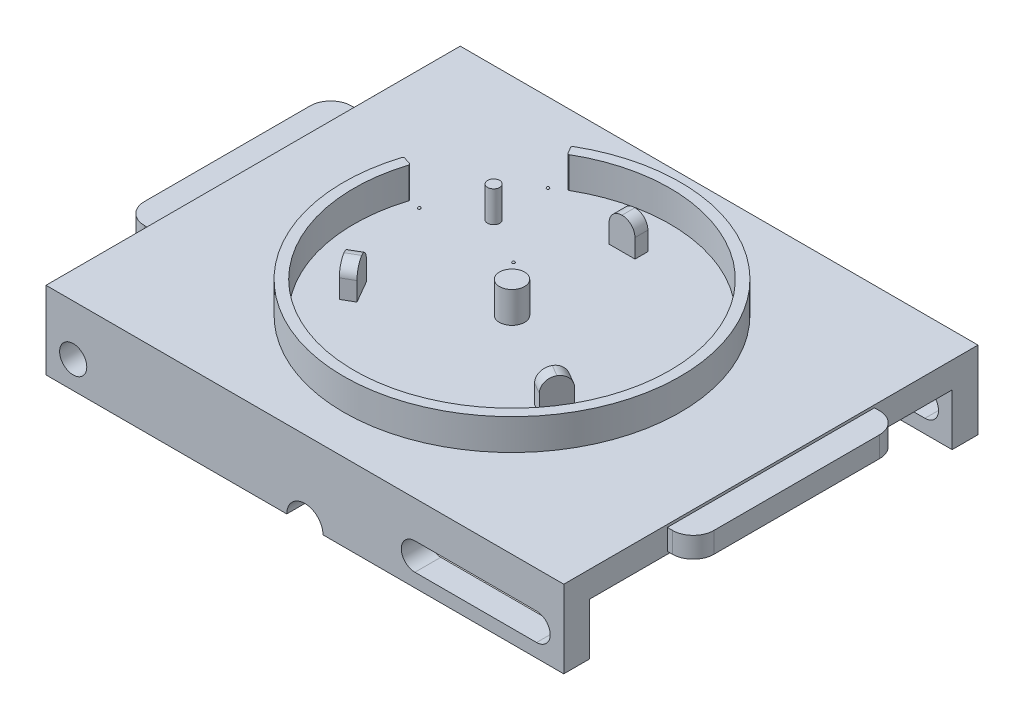
SolidWorks part; units mm, degrees
ref_plane "Vorne" through (0, 0, 0) normal (0, 0, 1) x (1, 0, 0)
ref_plane "Oben" through (0, 0, 0) normal (0, 1, 0) x (1, 0, 0)
ref_plane "Seite" through (0, 0, 0) normal (1, 0, 0) x (0, 0, -1)
sketch "Skizze1" plane through (0, 0, 0) normal (0, 1, 0) x (1, 0, 0)
  line L1 (100, -80) -> (-100, -80)
  line L2 (100, -80) -> (100, 80)
  line L3 (100, 80) -> (-100, 80)
  line L4 (-100, -80) -> (-100, 80)
  line L5 (100, -80) -> (-100, 80) construction
  line L6 (100, 80) -> (-100, -80) construction
  point P0 (0, 0)
  dimension "D1" = 160
  dimension "D2" = 200
extrude "Aufsatz-Linear austragen1" add sketch "Skizze1" along normal mid plane 10
sketch "Skizze2" plane through (0, -5, 0) normal (0, -1, 0) x (-1, 0, 0)
  line L0 (-100, 0) -> (100, 0) construction
  line L5 (100, -75) -> (-100, -75) construction
  line L6 (100, 70) -> (-100, 70)
  line L7 (100, 70) -> (100, 80)
  line L8 (100, 80) -> (-100, 80)
  line L9 (-100, 70) -> (-100, 80)
  line L10 (0, 80) -> (0, 70) construction
  line L15 (-100, -80) -> (-100, 80) construction
  line L16 (100, 80) -> (100, -80) construction
  line L17 (0, -80) -> (0, 80) construction
  line L18 (100, -80) -> (-100, -80) construction
  line L19 (-100, 80) -> (100, 80) construction
  line L20 (100, 75) -> (-100, 75) construction
  line L21 (0, -80) -> (0, -70) construction
  line L22 (-100, -70) -> (-100, -80)
  line L23 (100, -80) -> (-100, -80)
  line L24 (100, -70) -> (100, -80)
  line L25 (100, -70) -> (-100, -70)
  point P28 (0, -75)
  point P672 (0, 75)
  dimension "D1" = 200
  dimension "D2" = 10
  dimension "D3" = 80
extrude "Aufsatz-Linear austragen2" add sketch "Skizze2" along normal blind 20
sketch "Skizze3" plane through (0, 0, 0) normal (0, 0, 1) x (1, 0, 0)
  line L0 (42.5, -9.25) -> (89.5, -9.25)
  line L1 (42.5, -19.75) -> (89.5, -19.75)
  line L2 (100, -25) -> (-100, -25) construction
  line L3 (100, -25) -> (100, 5) construction
  line L4 (-100, -25) -> (-100, 5) construction
  line L5 (-7, -25) -> (7, -25)
  circle A0 centre (-89.5, -14.5) radius 5.25
  arc A1 (89.5, -19.75) -> (89.5, -9.25) centre (89.5, -14.5) ccw
  arc A2 (42.5, -9.25) -> (42.5, -19.75) centre (42.5, -14.5) ccw
  arc A3 (7, -25) -> (-7, -25) centre (0, -25) ccw
  dimension "D2" = 10.5
  dimension "D6" = 7
  dimension "D1" = 10.5
  dimension "D3" = 47
  dimension "D4" = 10.5
  dimension "D5" = 10.5
extrude "Schnitt-Linear austragen1" cut sketch "Skizze3" against normal through all both and the other way through all
sketch "Skizze4" plane through (0, 5, 0) normal (0, 1, 0) x (1, 0, 0)
  line L0 (-58.0351, 18.7863) -> (-61.8407, 20.0182)
  line L1 (-100, 80) -> (-100, -80) construction
  line L2 (-31.0675, 52.4958) -> (-33.1047, 55.9382)
  line L5 (0, 0) -> (-35.4514, 28.3612) construction
  line L6 (-35.4514, 28.3612) -> (-100, 80) construction
  circle A0 centre (0, 0) radius 4.85
  circle A3 centre (-35.4514, 28.3612) radius 2.35
  arc A4 (-61.8407, 20.0182) -> (-33.1047, 55.9382) centre (0, 0) ccw
  arc A5 (-58.0351, 18.7863) -> (-31.0675, 52.4958) centre (0, 0) ccw
  dimension "D1" = 9.7
  dimension "D4" = 4.7
  dimension "D7" = 4
  dimension "D3" = 46
  dimension "D5" = 61
  dimension "D2" = 45.4
extrude "Aufsatz-Linear austragen3" add sketch "Skizze4" along normal blind 12
chamfer "Fase1" distance 0.4 angle 45 4 edges at (-58.0351, 11, -18.7863) (-61.8407, 11, -20.0182) (-33.1047, 11, -55.9382) (-31.0675, 11, -52.4958)
sketch "Skizze6" plane through (0, 5, 0) normal (0, 1, 0) x (1, 0, 0)
  line L0 (0, 45) -> (-38.9711, -22.5) construction
  line L1 (-38.9711, -22.5) -> (38.9711, -22.5) construction
  line L2 (38.9711, -22.5) -> (0, 45) construction
  line L3 (0, 0) -> (-38.9711, -22.5) construction
  line L4 (0, 0) -> (38.9711, -22.5) construction
  line L5 (0, 0) -> (0, 45) construction
  line L6 (43.6362, -19.4199) -> (39.3061, -16.9199)
  line L7 (39.3061, -16.9199) -> (34.3061, -25.5801)
  line L8 (34.3061, -25.5801) -> (38.6362, -28.0801)
  line L9 (38.6362, -28.0801) -> (43.6362, -19.4199)
  line L10 (-34.3061, -25.5801) -> (-39.3061, -16.9199)
  line L11 (-39.3061, -16.9199) -> (-43.6362, -19.4199)
  line L12 (-43.6362, -19.4199) -> (-38.6362, -28.0801)
  line L13 (-38.6362, -28.0801) -> (-34.3061, -25.5801)
  line L14 (5, 42.5) -> (-5, 42.5)
  line L15 (-5, 42.5) -> (-5, 47.5)
  line L16 (-5, 47.5) -> (5, 47.5)
  line L17 (5, 47.5) -> (5, 42.5)
  line L18 (5, 47.5) -> (-5, 42.5) construction
  line L19 (-5, 47.5) -> (5, 42.5) construction
  line L20 (39.3061, -16.9199) -> (38.6362, -28.0801) construction
  line L21 (34.3061, -25.5801) -> (43.6362, -19.4199) construction
  line L22 (-38.6362, -28.0801) -> (-39.3061, -16.9199) construction
  line L23 (-43.6362, -19.4199) -> (-34.3061, -25.5801) construction
  circle A0 centre (0, 0) radius 45 construction
  point P3 (-38.9711, -22.5)
  point P4 (0, 45)
  point P5 (38.9711, -22.5)
  point P19 (0, 45)
  point P22 (38.9711, -22.5)
  point P23 (-38.9711, -22.5)
  dimension "D1" = 90
  dimension "D2" = 10
  dimension "D3" = 5
extrude "Aufsatz-Linear austragen4" add sketch "Skizze6" along normal blind 12.2 separate body
fillet "Verrundung1" radius 5 2 edges at (36.4711, 17.2, 26.8301) (41.4711, 17.2, 18.1699)
fillet "Verrundung2" radius 5 2 edges at (-36.4711, 17.2, 26.8301) (-41.4711, 17.2, 18.1699)
fillet "Verrundung3" radius 5 2 edges at (-5, 17.2, -45) (5, 17.2, -45)
sketch "Skizze7" plane through (0, 0, 0) normal (0, 1, 0) x (1, 0, 0)
  line L0 (-100, 40) -> (-110, 40)
  line L1 (-100, 80) -> (-100, -80) construction
  line L2 (-110, 40) -> (-110, -40)
  line L3 (-110, -40) -> (-100, -40)
  line L4 (100, 80) -> (-100, 80) construction
  line L5 (-100, 40) -> (-100, -40)
  line L6 (0, -50) -> (0, 50) construction
  line L7 (100, 40) -> (100, -40)
  line L8 (110, -40) -> (100, -40)
  line L9 (110, 40) -> (110, -40)
  line L10 (100, 40) -> (110, 40)
  dimension "D1" = 80
  dimension "D2" = 10
  dimension "D3" = 40
extrude "Aufsatz-Linear austragen5" add sketch "Skizze7" along normal mid plane 8
fillet "Verrundung4" radius 8 4 edges at (110, 0, 40) (110, 0, -40) (-110, 0, -40) (-110, 0, 40)
sketch "Skizze8" plane through (0, 5, 0) normal (0, 1, 0) x (1, 0, 0)
  line L0 (-35.4514, 49.3612) -> (-53.638, 17.8612) construction
  line L1 (-53.638, 17.8612) -> (-17.2649, 17.8612) construction
  line L2 (-17.2649, 17.8612) -> (-35.4514, 49.3612) construction
  circle A0 centre (-35.4514, 28.3612) radius 21 construction
  circle A1 centre (-35.4514, 49.3612) radius 0.5
  circle A2 centre (-53.638, 17.8612) radius 0.5
  circle A3 centre (-17.2649, 17.8612) radius 0.5
  dimension "D1" = 42
  dimension "D2" = 1
extrude "Aufsatz-Linear austragen6" add sketch "Skizze8" along normal blind 0.5
fillet "Verrundung5" radius 0.5 3 edges at (-53.638, 5.5, -17.3612) (-17.2649, 5.5, -17.3612) (-35.4514, 5.5, -48.8612)
